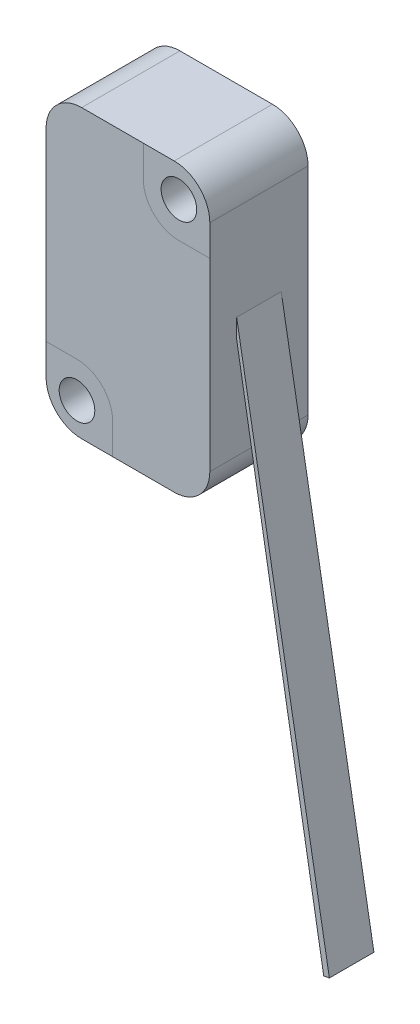
SolidWorks part; units mm, degrees
ref_plane "Front Plane" through (0, 0, 0) normal (0, 0, 1) x (1, 0, 0)
ref_plane "Top Plane" through (0, 0, 0) normal (0, 1, 0) x (1, 0, 0)
ref_plane "Right Plane" through (0, 0, 0) normal (1, 0, 0) x (0, 0, -1)
sketch "Sketch1" plane through (0, 0, 0) normal (0, 0, 1) x (1, 0, 0)
  line L1 (-7.9375, -13.9065) -> (7.9375, -13.9065)
  line L2 (-7.9375, -13.9065) -> (-7.9375, 13.9065)
  line L3 (-7.9375, 13.9065) -> (7.9375, 13.9065)
  line L4 (7.9375, -13.9065) -> (7.9375, 13.9065)
  line L5 (-7.9375, -13.9065) -> (7.9375, 13.9065) construction
  line L6 (-7.9375, 13.9065) -> (7.9375, -13.9065) construction
  point P0 (0, 0)
  dimension "D1" = 15.875
  dimension "D2" = 27.813
extrude "Boss-Extrude1" add sketch "Sketch1" along normal mid plane 9.525 contours L3 L4 L1 L2
sketch "Sketch2" plane through (0, 0, 0) normal (0, 0, 1) x (1, 0, 0)
  line L0 (7.9375, 1.2065) -> (16.9264, -49.7723)
  line L1 (7.9375, -13.9065) -> (7.9375, 13.9065) construction
  line L2 (16.9264, -49.7723) -> (16.3761, -49.8693)
  line L3 (16.3761, -49.8693) -> (7.9375, -0.655)
  line L5 (7.9375, -0.655) -> (7.9375, 1.2065)
  line L8 (-7.9375, 13.9065) -> (-7.9375, -13.9065)
  line L9 (-7.9375, -13.9065) -> (7.9375, -13.9065)
  line L10 (7.9375, -13.9065) -> (7.9375, 13.9065)
  line L11 (7.9375, 13.9065) -> (-7.9375, 13.9065)
  line L14 (7.9375, 1.2065) -> (7.9375, 13.9065)
  dimension "D1" = 12.7
  dimension "D2" = 0.5588
  dimension "D3" = 10
  dimension "D5" = 51.7652
  dimension "D4" = 0
extrude "Boss-Extrude2" add sketch "Sketch2" along normal mid plane 4.318 contours L0 L2 L3 L5
hole_wizard "#29 (0.136) Diameter Hole1" positions "Sketch3" profile "Sketch4" hole size "#29" standard "ANSI Inch" end condition through all
sketch "Sketch3" plane through (0, 0, 4.7625) normal (0, 0, 1) x (1, 0, 0)
  line L1 (-7.9375, -13.9065) -> (7.9375, -13.9065) construction
  line L2 (-7.9375, -13.9065) -> (-7.9375, 13.9065) construction
  circle A0 centre (-4.9403, -10.9093) radius 1.7272
  point P2 (-4.9403, -10.9093)
  point P23 (4.9403, 10.9093)
  dimension "D2" = 3.4544
  dimension "D1" = 2.9972
  dimension "D3" = 2.9972
sketch "Sketch4" plane through (-4.9403, -10.9093, 4.7625) normal (1, 0, 0) x (0, -1, 0)
  line L0 (0, 0) -> (0, 9.525)
  line L1 (0, 9.525) -> (1.7272, 9.525)
  line L2 (1.7272, 9.525) -> (1.7272, 0)
  line L5 (1.7272, 0) -> (0, 0)
  line L11 (0, -6.35) -> (0, 107.95) construction
  dimension "Thru Hole Dia." = 3.4544
  dimension "Thru Hole Depth" = 9.525
fillet "Fillet1" radius 3.4544 4 edges at (7.9375, -13.9065, 0) (-7.9375, -13.9065, 0) (7.9375, 13.9065, 0) (-7.9375, 13.9065, 0)
sketch "Sketch5" plane through (0, 0, 4.7625) normal (0, 0, 1) x (1, 0, 0)
  line L0 (1.4859, 13.9065) -> (1.4859, 10.9093)
  line L1 (-4.4831, 13.9065) -> (4.4831, 13.9065) construction
  line L2 (7.9375, 7.4549) -> (4.9403, 7.4549)
  line L3 (7.9375, -10.4521) -> (7.9375, 10.4521) construction
  line L4 (1.4859, 13.9065) -> (4.4831, 13.9065)
  line L5 (7.9375, 7.4549) -> (7.9375, 10.4521)
  line L6 (5.2388, 0) -> (-5.2388, 0) construction
  line L7 (7.9375, -10.4521) -> (7.9375, 7.4549) construction
  line L8 (7.9375, -7.4549) -> (7.9375, -10.4521) construction
  line L9 (1.4859, -13.9065) -> (4.4831, -13.9065) construction
  line L10 (7.9375, -7.4549) -> (4.9403, -7.4549) construction
  line L11 (1.4859, -13.9065) -> (1.4859, -10.9093) construction
  line L12 (0, -5.2388) -> (0, 5.2388) construction
  line L13 (-1.4859, -13.9065) -> (-1.4859, -10.9093)
  line L14 (-7.9375, -7.4549) -> (-4.9403, -7.4549)
  line L15 (-1.4859, -13.9065) -> (-4.4831, -13.9065)
  line L16 (-7.9375, -7.4549) -> (-7.9375, -10.4521)
  arc A0 (1.4859, 10.9093) -> (4.9403, 7.4549) centre (4.9403, 10.9093) ccw
  arc A1 (7.9375, 10.4521) -> (4.4831, 13.9065) centre (4.4831, 10.4521) ccw construction
  circle A2 centre (4.9403, 10.9093) radius 1.7272 construction
  arc A3 (7.9375, 10.4521) -> (4.4831, 13.9065) centre (4.4831, 10.4521) ccw
  arc A4 (7.9375, -10.4521) -> (4.4831, -13.9065) centre (4.4831, -10.4521) cw construction
  arc A5 (1.4859, -10.9093) -> (4.9403, -7.4549) centre (4.9403, -10.9093) cw construction
  arc A6 (-1.4859, -10.9093) -> (-4.9403, -7.4549) centre (-4.9403, -10.9093) ccw
  arc A7 (-7.9375, -10.4521) -> (-4.4831, -13.9065) centre (-4.4831, -10.4521) ccw
  point P7 (0, 0)
  point P11 (0, 0)
  point P14 (3.0004, 8.0511)
split line "Split Line1"
